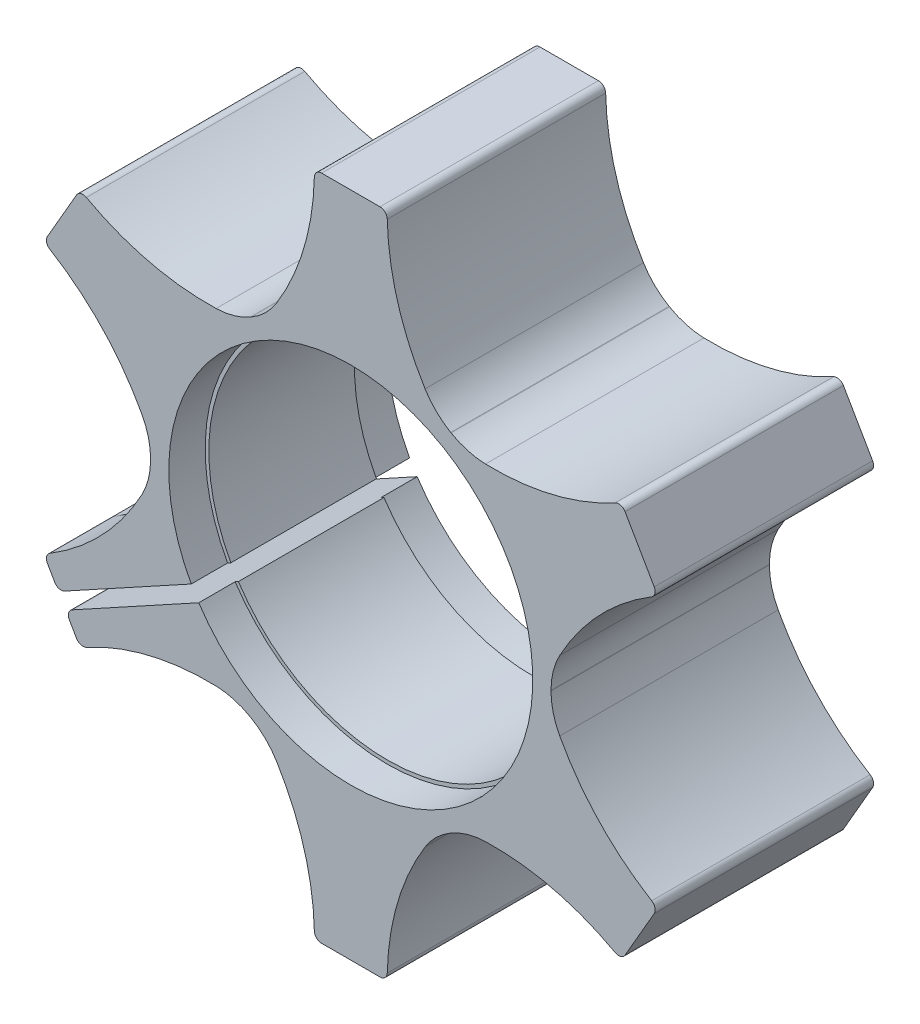
SolidWorks part; units mm, degrees
material "PP Copolymer"
ref_plane "Front Plane" through (0, 0, 0) normal (0, 0, 1) x (1, 0, 0)
ref_plane "Top Plane" through (0, 0, 0) normal (0, 1, 0) x (1, 0, 0)
ref_plane "Right Plane" through (0, 0, 0) normal (1, 0, 0) x (0, 0, -1)
sketch "Sketch1" plane through (0, 0, 0) normal (0, 0, 1) x (1, 0, 0)
  line L0 (-1.27, 11.6367) -> (1.27, 11.6367)
  line L1 (9.4427, 6.9182) -> (10.7127, 4.7185)
  line L2 (10.7127, -4.7185) -> (9.4427, -6.9182)
  line L3 (1.27, -11.6367) -> (-1.27, -11.6367)
  line L4 (-9.4427, -6.9182) -> (-9.9506, -6.0384)
  line L5 (-10.7127, 4.7185) -> (-9.4427, 6.9182)
  line L6 (-10.2047, -5.5983) -> (-6.124, -3.3596)
  line L7 (-9.9506, -6.0384) -> (-5.8634, -3.7961)
  line L8 (-10.2047, -5.5983) -> (-10.7127, -4.7185)
  arc A0 (-6.124, -3.3596) -> (-5.8634, -3.7961) centre (0, 0) ccw
  arc A1 (-3.008, 6.3041) -> (-1.27, 11.6367) centre (-10.1598, 11.5846) ccw
  arc A2 (1.27, 11.6367) -> (3.008, 6.3041) centre (10.1598, 11.5846) ccw
  arc A4 (3.9555, 5.7571) -> (9.4427, 6.9182) centre (4.9527, 14.591) ccw
  arc A5 (10.7127, 4.7185) -> (6.9635, 0.547) centre (15.1125, -3.0064) ccw
  arc A6 (6.9635, -0.547) -> (10.7127, -4.7185) centre (15.1125, 3.0064) ccw
  arc A7 (9.4427, -6.9182) -> (3.9555, -5.7571) centre (4.9527, -14.591) ccw
  arc A8 (3.008, -6.3041) -> (1.27, -11.6367) centre (10.1598, -11.5846) ccw
  arc A9 (-1.27, -11.6367) -> (-3.008, -6.3041) centre (-10.1598, -11.5846) ccw
  arc A10 (-3.9555, -5.7571) -> (-9.4427, -6.9182) centre (-4.9527, -14.591) ccw
  arc A11 (-10.7127, -4.7185) -> (-6.9635, -0.547) centre (-15.1125, 3.0064) ccw
  arc A12 (-6.9635, 0.547) -> (-10.7127, 4.7185) centre (-15.1125, -3.0064) ccw
  arc A13 (-9.4427, 6.9182) -> (-3.9555, 5.7571) centre (-4.9527, 14.591) ccw
  arc A14 (-3.9555, -5.7571) -> (-3.008, -6.3041) centre (0, 0) ccw
  arc A15 (3.008, -6.3041) -> (3.9555, -5.7571) centre (0, 0) ccw
  arc A16 (6.9635, -0.547) -> (6.9635, 0.547) centre (0, 0) ccw
  arc A17 (3.9555, 5.7571) -> (3.008, 6.3041) centre (0, 0) ccw
  arc A18 (-3.008, 6.3041) -> (-3.9555, 5.7571) centre (0, 0) ccw
  arc A19 (-6.9635, 0.547) -> (-6.9635, -0.547) centre (0, 0) ccw
  point P9 (0, 11.6367)
  dimension "D1" = 13.97
  dimension "D2" = 6
  dimension "D3" = 8.89
  dimension "D4" = 1.27
  dimension "D5" = 3.008
  dimension "D6" = 4.9527
  dimension "D7" = 5.8634
extrude "Boss-Extrude2" add sketch "Sketch1" along normal mid plane 7.62 contours A13 A18 A1 L0 A2 A17 A4 L1 A5 A16 A6 L2 A7 A15 A8 L3 A9 A14 A10 L4 L7 A0 L6 L8 A11 A19 A12 L5
sketch "Sketch3" plane through (0, 0, 3.81) normal (0, 0, 1) x (1, 0, 0)
  circle A0 centre (0, 0) radius 6.35
  dimension "D1" = 12.7
extrude "Cut-Extrude1" cut sketch "Sketch3" against normal blind 12.7
ref_plane "Plane1" through (0, 0, 0) normal (0, 0, 1) x (1, 0, 0)
sketch "Sketch4" plane through (0, 0, 0) normal (0, 0, 1) x (1, 0, 0)
  circle A1 centre (0, 0) radius 6.35
  circle A2 centre (0, 0) radius 6.223
  dimension "D1" = 12.7
  dimension "D2" = 12.446
extrude "Boss-Extrude3" add sketch "Sketch4" along normal mid plane 5.08
sketch "Sketch7" plane through (0, 0, -3.81) normal (0, 0, -1) x (-1, 0, 0)
  line L0 (6.124, -3.3596) -> (4.841, -2.6558)
  line L1 (5.8634, -3.7961) -> (4.5967, -3.1012)
  line L2 (4.5967, -3.1012) -> (4.841, -2.6558)
  line L3 (10.2047, -5.5983) -> (6.124, -3.3596) construction
  line L6 (5.8634, -3.7961) -> (6.124, -3.9391)
  line L7 (9.9506, -6.0384) -> (5.8634, -3.7961) construction
  line L8 (6.124, -3.9391) -> (6.3683, -3.4937)
  line L9 (6.3683, -3.4937) -> (6.124, -3.3596)
  dimension "D1" = 5.8717
extrude "Cut-Extrude5" cut sketch "Sketch7" against normal blind 8.89 contours L2 L0 L9 L8 L6 L1
ref_plane "Plane2" through (0.733, -1.3361, 0) normal (0.481, -0.8767, 0) x (-0.8767, -0.481, 0)
sketch "Sketch8" plane through (0.733, -1.3361, 0) normal (0.481, -0.8767, 0) x (-0.8767, -0.481, 0)
  line L0 (11.6062, 1.5875) -> (11.6062, -1.5875)
  line L1 (11.6062, -3.81) -> (11.6062, 3.81) construction
  line L2 (11.6062, -1.5875) -> (8.4312, -1.5875)
  line L3 (11.6062, 1.5875) -> (8.4312, 1.5875)
  line L4 (8.4312, 1.5875) -> (8.4312, -1.5875)
  line L5 (8.4312, 1.5875) -> (11.6062, -1.5875) construction
  line L6 (8.4312, -1.5875) -> (11.6062, 1.5875) construction
  line L7 (-11.7839, 0) -> (11.7839, 0) construction
  point P4 (10.0187, 0)
  dimension "D1" = 3.175
extrude "Cut-Extrude6" cut sketch "Sketch8" along normal blind 2.54
ref_plane "Plane3" through (0.1222, -0.2227, 0) normal (0.481, -0.8767, 0) x (-0.8767, -0.481, 0)
mirror "Mirror2" about plane through (0.1222, -0.2227, 0) normal (0.481, -0.8767, 0) of "Cut-Extrude6"
ref_point "Point1"
hole_wizard "1/16 (0.0625) Diameter Hole2" positions "Sketch16" profile "Sketch17" hole size "1/16" standard "ANSI Inch" end condition through all
sketch "Sketch16" plane through (0.733, -1.3361, 0) normal (0.481, -0.8767, 0) x (-0.8767, -0.481, 0)
  point P0 (9.7673, 0)
sketch "Sketch17" plane through (-7.8303, -6.034, 0) normal (0, 0, 1) x (0.8767, 0.481, 0)
  line L0 (0, 0) -> (0, 16.8788)
  line L1 (0, 16.8788) -> (0.7937, 16.8788)
  line L2 (0.7937, 16.8788) -> (0.7937, 0)
  line L5 (0.7937, 0) -> (0, 0)
  line L11 (0, -6.35) -> (0, 107.95) construction
  dimension "Thru Hole Dia." = 1.5875
  dimension "Thru Hole Depth" = 16.8788
fillet "Fillet1" radius 2.54 12 edges at (-3.9555, -5.7571, 0) (-3.008, -6.3041, 0) (-6.9635, 0.547, 0) (-6.9635, -0.547, 0) (-3.9555, 5.7571, 0) (-3.008, 6.3041, 0) (3.008, 6.3041, 0) (3.9555, 5.7571, 0) (6.9635, 0.547, 0) (6.9635, -0.547, 0) (3.9555, -5.7571, 0) (3.008, -6.3041, 0)
fillet "Fillet2" radius 0.254 13 edges at (-10.2047, -5.5983, 0) (-9.4427, -6.9182, 0) (-1.27, -11.6367, 0) (1.27, -11.6367, 0) (10.7127, 4.7185, 0) (9.4427, 6.9182, 0) (9.4427, -6.9182, 0) (10.7127, -4.7185, 0) (1.27, 11.6367, 0) (-9.4427, 6.9182, 0) (-1.27, 11.6367, 0) (-10.7127, -4.7185, 0) (-9.9506, -6.0384, 0)
fillet "Fillet3" radius 0.254 1 edges at (-10.7127, 4.7185, 0)
